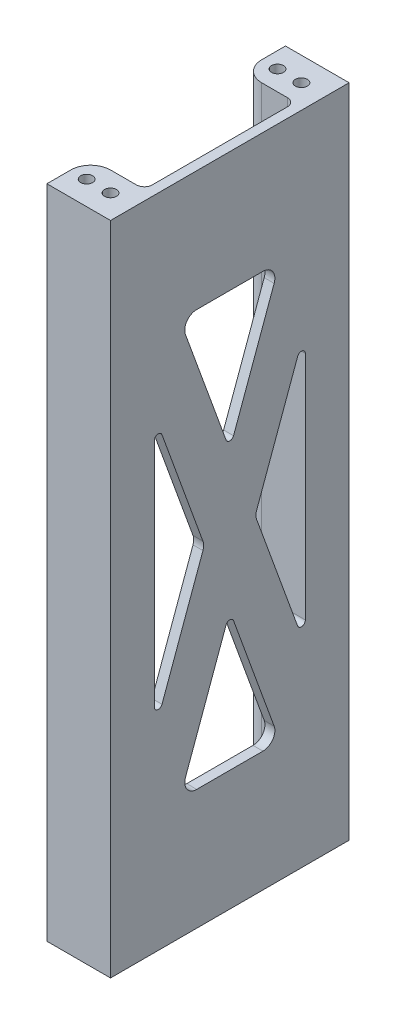
SolidWorks part; units mm, degrees
ref_plane "Front Plane" through (0, 0, 0) normal (0, 0, 1) x (1, 0, 0)
ref_plane "Top Plane" through (0, 0, 0) normal (0, 1, 0) x (1, 0, 0)
ref_plane "Right Plane" through (0, 0, 0) normal (1, 0, 0) x (0, 0, -1)
sketch "Sketch2" plane through (0, 0, 0) normal (0, 1, 0) x (1, 0, 0)
  line L0 (-26.899, -6.9663) -> (-13.399, -6.9663)
  line L1 (-22.899, -49.9663) -> (-12.2267, -49.9663) construction
  line L2 (-26.899, -55.9663) -> (-26.899, -44.9663)
  line L3 (-10.899, -55.9663) -> (-26.899, -55.9663)
  line L4 (-13.399, -44.9663) -> (-13.399, -6.9663)
  line L5 (-10.899, -25.9663) -> (-13.399, -25.9663) construction
  line L6 (-26.899, -44.9663) -> (-13.399, -44.9663)
  line L7 (-10.899, -55.9663) -> (-10.899, 4.0337)
  line L9 (-22.899, -1.9663) -> (-12.2267, -1.9663) construction
  line L11 (-10.899, 4.0337) -> (-26.899, 4.0337)
  line L12 (-26.899, 4.0337) -> (-26.899, -6.9663)
  circle A0 centre (-16.899, -1.9663) radius 1.5
  circle A1 centre (-22.899, -1.9663) radius 1.5
  circle A2 centre (-22.899, -49.9663) radius 1.5
  circle A3 centre (-16.899, -49.9663) radius 1.5
  dimension "D2" = 6
  dimension "D4" = 2.5
  dimension "D5" = 3
  dimension "D9" = 16
  dimension "D1" = 30
  dimension "D3" = 6
  dimension "D6" = 11
extrude "Boss-Extrude1" add sketch "Sketch2" along normal blind 165 contours L2 L7 L4 L6 A1 A0 region at (-26.278, 0, 1.4663)
sketch "Sketch3" plane through (-10.899, 0, 0) normal (1, 0, 0) x (0, 0, -1)
  line L0 (-55.9663, 0) -> (4.0337, 165) construction
  line L1 (-55.9663, 165) -> (4.0337, 0) construction
  line L3 (-6.9663, 30.25) -> (-44.9663, 30.25)
  line L4 (-6.9663, 30.25) -> (-6.9663, 134.75)
  line L5 (-6.9663, 134.75) -> (-44.9663, 134.75)
  line L6 (-44.9663, 30.25) -> (-44.9663, 134.75)
  line L7 (-6.9663, 30.25) -> (-44.9663, 134.75) construction
  line L8 (-6.9663, 134.75) -> (-44.9663, 30.25) construction
  line L9 (-50.3275, -2.0505) -> (9.6725, 162.9495)
  line L10 (-61.605, 162.9495) -> (-1.605, -2.0505)
  line L11 (-61.605, 2.0505) -> (-1.605, 167.0505)
  line L12 (-50.3275, 167.0505) -> (9.6725, 2.0505)
  line L13 (4.0337, 165) -> (4.0337, 0) construction
  line L14 (-55.9663, 0) -> (4.0337, 0) construction
  line L15 (-55.9663, 165) -> (-55.9663, 0) construction
  line L16 (-55.9663, 165) -> (4.0337, 165) construction
  line L17 (4.0337, 165) -> (4.0337, 0) construction
  point P8 (-25.9663, 82.5)
  dimension "D1" = 11
  dimension "D2" = 6
  dimension "D3" = 6
extrude "Cut-Extrude1" cut sketch "Sketch3" against normal through all contours L5 L12 L11 | L6 L11 L10 | L9 L12 L4 | L10 L9 L3 region at (-10.899, 41.8143, 25.9663) region at (-10.899, 82.5, 11.1715) region at (-10.899, 82.5, 40.7611) region at (-10.899, 123.1857, 25.9663)
fillet "Fillet1" radius 1 6 edges at (-12.149, 117.193, 6.9663) (-12.149, 117.193, 44.9663) (-12.149, 47.807, 6.9663) (-12.149, 47.807, 44.9663) (-12.149, 100.057, 25.9663) (-12.149, 64.943, 25.9663)
fillet "Fillet2" radius 3 6 edges at (-12.149, 134.75, 13.3507) (-12.149, 134.75, 38.5819) (-12.149, 30.25, 13.3507) (-12.149, 30.25, 38.5819) (-12.149, 82.5, 19.5819) (-12.149, 82.5, 32.3507)
fillet "Fillet4" radius 5 2 edges at (-26.899, 82.5, 44.9663) (-26.899, 82.5, 6.9663)
fillet "Fillet3" radius 2 4 edges at (-13.399, 138.2584, 44.9663) (-13.399, 26.7416, 44.9663) (-13.399, 138.2584, 6.9663) (-13.399, 26.7416, 6.9663)
